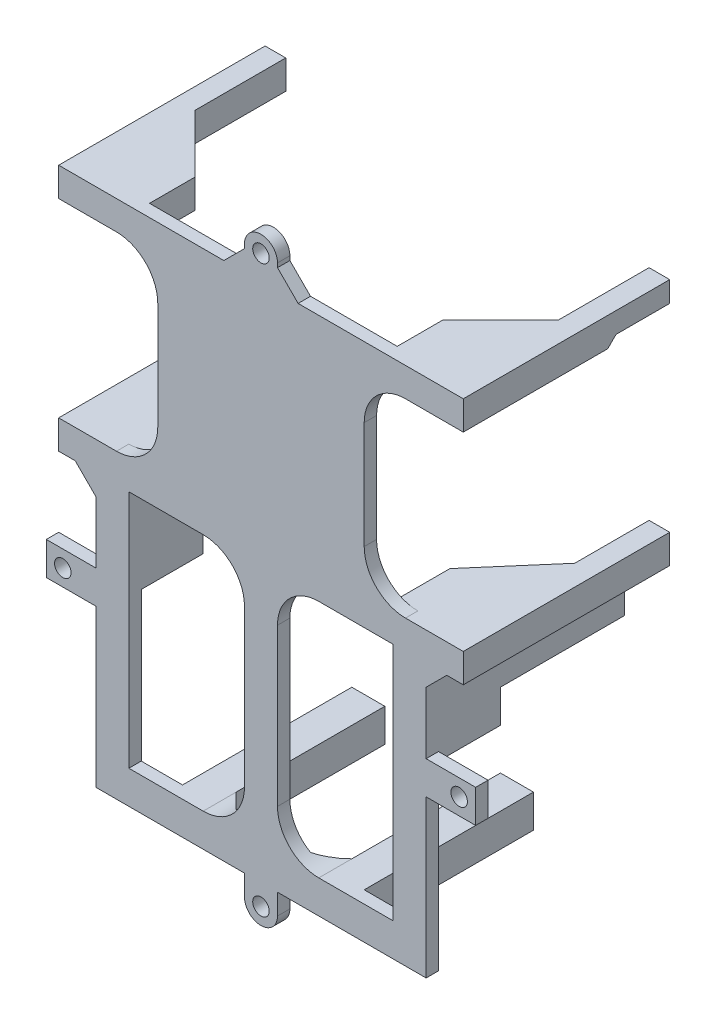
SolidWorks part; units mm, degrees
ref_plane "Piano frontale" through (0, 0, 0) normal (0, 0, 1) x (1, 0, 0)
ref_plane "Piano superiore" through (0, 0, 0) normal (0, 1, 0) x (1, 0, 0)
ref_plane "Piano destro" through (0, 0, 0) normal (1, 0, 0) x (0, 0, -1)
sketch "Schizzo1" plane through (0, 0, 0) normal (0, 0, 1) x (1, 0, 0)
  line L0 (0, 0) -> (0, 70) construction
  line L1 (-48, 23) -> (48, 23) construction
  line L2 (0, 70) -> (0, 0) construction
  line L3 (4, 70) -> (4, 27)
  line L4 (-4, 70) -> (-4, 27)
  line L5 (-48, 23) -> (48, 23) construction
  line L6 (52, 27) -> (52, 18)
  line L7 (-52, 27) -> (-52, 18)
  line L8 (4, 18) -> (4, -16)
  line L9 (4, 27) -> (52, 27)
  line L10 (-4, 18) -> (-4, -16)
  line L11 (4, 18) -> (52, 18)
  line L12 (-4, 18) -> (-52, 18)
  line L13 (-4, 27) -> (-52, 27)
  line L14 (-48, -20) -> (48, -20) construction
  line L15 (-4, -24) -> (-4, -67)
  line L16 (-52, -16) -> (-4, -16)
  line L17 (-52, -16) -> (-52, -24)
  line L18 (-52, -24) -> (-4, -24)
  line L19 (52, -16) -> (52, -24)
  line L20 (4, -16) -> (52, -16)
  line L21 (4, -24) -> (4, -67)
  line L22 (4, -24) -> (52, -24)
  circle A0 centre (0, 70) radius 2
  circle A1 centre (48, 23) radius 2
  circle A2 centre (-48, 23) radius 2
  arc A3 (4, 70) -> (-4, 70) centre (0, 70) ccw
  arc A4 (-4, -67) -> (4, -67) centre (0, -67) ccw
  circle A5 centre (0, -67) radius 2
  circle A6 centre (-48, -20) radius 2
  circle A7 centre (48, -20) radius 2
  point P8 (0, 35)
  point P13 (0, 20)
  dimension "D1" = 4
  dimension "D2" = 4
  dimension "D3" = 4
  dimension "D10" = 137
  dimension "D11" = 4
  dimension "D6" = 4
  dimension "D18" = 4
  dimension "D19" = 4
  dimension "D4" = 70
  dimension "D5" = 8
  dimension "D7" = 23
  dimension "D8" = 48
  dimension "D9" = 48
  dimension "D12" = 4
  dimension "D13" = 48
  dimension "D14" = 47
  dimension "D15" = 47
  dimension "D16" = 48
  dimension "D17" = 48
  dimension "D20" = 8
  dimension "D21" = 4
extrude "Estrusione-Estrusione1" add sketch "Schizzo1" along normal blind 3
sketch "Schizzo2" plane through (0, 0, 0) normal (0, 0, 1) x (1, 0, 0)
  line L0 (-42, 57) -> (-3.9212, 57)
  line L1 (-49, 64) -> (-3.9212, 64)
  line L2 (-49, 64) -> (-49, 26)
  line L3 (-49, 4) -> (-40, 4)
  line L4 (49, 64) -> (49, 26)
  line L5 (42, 57) -> (42, 26)
  line L6 (-42, 11) -> (-3.9212, 11)
  line L7 (-42, 57) -> (-42, 26)
  line L8 (-3.9212, 64) -> (-3.9212, 57)
  line L9 (3.9902, 64) -> (3.9902, 57)
  line L10 (3.9902, 64) -> (49, 64)
  line L11 (3.9902, 57) -> (42, 57)
  line L12 (-49, 64) -> (49, 64) construction
  line L13 (-3.9212, 11) -> (-3.9212, 4)
  line L14 (-42, 57) -> (42, 57) construction
  line L15 (3.9902, 11) -> (3.9902, 4)
  line L16 (3.9902, 11) -> (42, 11)
  line L17 (3.9902, 4) -> (32, 4)
  line L18 (-42, 11) -> (42, 11) construction
  line L19 (49, 26) -> (42, 26)
  line L20 (-49, 4) -> (49, 4) construction
  line L22 (-32, 4) -> (-3.9212, 4)
  line L23 (-49, 18) -> (-42, 18)
  line L24 (-40, 4) -> (-40, -62)
  line L25 (-40, -62) -> (40, -62)
  line L26 (-42, 26) -> (-49, 26)
  line L27 (42, 18) -> (42, 11)
  line L28 (49, 18) -> (49, 4)
  line L29 (42, 57) -> (42, 11) construction
  line L30 (-49, 18) -> (-49, 4)
  line L31 (49, 64) -> (49, 4) construction
  line L32 (-42, 18) -> (-42, 11)
  line L33 (-49, 64) -> (-49, 4) construction
  line L34 (42, 18) -> (49, 18)
  line L35 (-42, 57) -> (-42, 11) construction
  line L36 (40, 4) -> (40, -62)
  line L37 (40, 4) -> (49, 4)
  line L39 (-32, 4) -> (-32, -54)
  line L40 (-32, -54) -> (32, -54)
  line L41 (32, 4) -> (32, -54)
  circle A0 centre (0, 70) radius 2 construction
  circle A1 centre (0, -67) radius 2 construction
  dimension "D9" = 5
  dimension "D1" = 98
  dimension "D2" = 49
  dimension "D3" = 60
  dimension "D4" = 6
  dimension "D6" = 80
  dimension "D7" = 40
  dimension "D8" = 8
  dimension "D10" = 8
  dimension "D11" = 8
  dimension "D5" = 7
extrude "Estrusione-Estrusione2" add sketch "Schizzo2" along normal blind 3
sketch "Schizzo3" plane through (0, 0, 0) normal (0, 0, -1) x (-1, 0, 0)
  line L0 (-44, 59) -> (-49, 64) construction
  line L1 (-49, 64) -> (-44, 64)
  line L2 (-49, 64) -> (-49, 59)
  line L3 (-49, 59) -> (-44, 59)
  line L4 (-44, 64) -> (-44, 59)
  line L5 (49, 64) -> (44, 64)
  line L6 (49, 64) -> (49, 59)
  line L7 (49, 59) -> (44, 59)
  line L8 (44, 64) -> (44, 59)
  line L9 (49, 4) -> (44, 4)
  line L10 (49, 4) -> (49, 9)
  line L11 (49, 9) -> (44, 9)
  line L12 (44, 4) -> (44, 9)
  line L13 (-49, 4) -> (-44, 4)
  line L14 (-49, 4) -> (-49, 9)
  line L15 (-49, 9) -> (-44, 9)
  line L16 (-44, 4) -> (-44, 9)
  line L17 (44, 59) -> (49, 64) construction
  line L18 (44, 9) -> (49, 4) construction
  line L19 (-44, 9) -> (-49, 4) construction
  line L20 (-40, 4) -> (-49, 4) construction
  dimension "D1" = 5
  dimension "D2" = 5
  dimension "D3" = 5
  dimension "D4" = 5
  dimension "D5" = 5
  dimension "D6" = 5
  dimension "D7" = 5
  dimension "D8" = 5
extrude "Estrusione-Estrusione3" add sketch "Schizzo3" along normal blind 47
sketch "Schizzo4" plane through (0, 0, -47) normal (0, 0, -1) x (-1, 0, 0)
  line L0 (-49, 64) -> (-44, 59) construction
  line L1 (44, 59) -> (49, 64) construction
  line L2 (44, 9) -> (49, 4) construction
  line L3 (-49, 4) -> (-44, 9) construction
  line L4 (-49, 4) -> (-44, 4) construction
  circle A0 centre (-46.5, 61.5) radius 1.25
  circle A1 centre (46.5, 61.5) radius 1.25
  circle A2 centre (46.5, 6.5) radius 1.25
  circle A3 centre (-46.5, 6.5) radius 1.25
  dimension "D1" = 2.5
  dimension "D2" = 2.5
  dimension "D3" = 2.5
  dimension "D4" = 2.5
extrude "Taglio-Estrusione1" cut sketch "Schizzo4" against normal blind 15
sketch "Schizzo5" plane through (0, 4, 0) normal (0, -1, 0) x (1, 0, 0)
  line L0 (-44, 0) -> (-19, 0)
  line L1 (-44, 0) -> (-40, 0) construction
  line L2 (-19, 0) -> (-44, -29)
  line L3 (-44, -47) -> (-44, 0) construction
  line L4 (-44, -29) -> (-44, 0)
  line L5 (19, 0) -> (44, 0)
  line L6 (40, 0) -> (44, 0) construction
  line L7 (4, 0) -> (32, 0) construction
  line L9 (44, 0) -> (44, -29)
  line L10 (44, -47) -> (44, 0) construction
  line L11 (44, -29) -> (19, 0)
  dimension "D1" = 25
  dimension "D2" = 29
  dimension "D3" = 25
  dimension "D4" = 29
extrude "Estrusione-Estrusione4" add sketch "Schizzo5" against normal blind 5
sketch "Schizzo6" plane through (0, 64, 0) normal (0, 1, 0) x (1, 0, 0)
  line L0 (-44, 25) -> (-19, 0)
  line L1 (-19, 0) -> (-44, 0)
  line L2 (-44, 0) -> (-44, 25)
  line L3 (44, 25) -> (19, 0)
  line L4 (19, 0) -> (44, 0)
  line L5 (44, 0) -> (44, 25)
extrude "Estrusione-Estrusione5" add sketch "Schizzo6" against normal blind 5
sketch "Schizzo9" plane through (0, 0, 0) normal (0, 0, -1) x (-1, 0, 0)
  line L0 (-4, 57) -> (-42, 57) construction
  line L1 (-25, 57) -> (25, 57)
  line L2 (-25, 57) -> (-25, 11)
  line L3 (-25, 11) -> (25, 11)
  line L4 (25, 57) -> (25, 11)
  line L5 (4, 11) -> (42, 11) construction
  circle A0 centre (0, 70) radius 2 construction
  dimension "D1" = 50
  dimension "D2" = 25
extrude "Estrusione-Estrusione8" add sketch "Schizzo9" against normal blind 3
chamfer "Smusso1" distance 5 angle 45 2 edges at (-4, 64, 1.5) (4, 64, 1.5)
sketch "Schizzo11" plane through (0, 0, 0) normal (0, 0, -1) x (-1, 0, 0)
  line L1 (-42, 57) -> (-25, 57)
  line L2 (-42, 57) -> (-42, 11)
  line L3 (-42, 11) -> (-25, 11)
  line L4 (-25, 57) -> (-25, 11)
  line L5 (25, 57) -> (42, 57)
  line L6 (25, 57) -> (25, 11)
  line L7 (25, 11) -> (42, 11)
  line L8 (42, 57) -> (42, 11)
  line L9 (-32, 4) -> (32, 4)
  line L10 (-32, 4) -> (-32, -54)
  line L11 (-32, -54) -> (32, -54)
  line L12 (32, 4) -> (32, -54)
extrude "Taglio-Estrusione3" cut sketch "Schizzo11" against normal blind 10
sketch "Schizzo12" plane through (0, 4, 0) normal (0, -1, 0) x (1, 0, 0)
  line L0 (-40, 0) -> (-4, 0) construction
  line L1 (-30, 0) -> (30, 0)
  line L2 (-30, 0) -> (-30, -20)
  line L3 (-30, -20) -> (30, -20)
  line L4 (30, 0) -> (30, -20)
  dimension "D1" = 60
  dimension "D2" = 30
  dimension "D3" = 20
extrude "Taglio-Estrusione4" cut sketch "Schizzo12" against normal blind 60
sketch "Schizzo13" plane through (0, 0, 0) normal (0, 0, -1) x (-1, 0, 0)
  line L0 (25, 11) -> (42, 11) construction
  line L1 (25, 57) -> (52, 57)
  line L2 (25, 57) -> (25, 11)
  line L3 (25, 11) -> (52, 11)
  line L4 (52, 57) -> (52, 11)
  line L5 (52, 27) -> (52, 18) construction
  line L6 (-52, 18) -> (-52, 27) construction
  line L7 (-25, 57) -> (-52, 57)
  line L8 (-25, 57) -> (-25, 11)
  line L9 (-25, 11) -> (-52, 11)
  line L10 (-52, 57) -> (-52, 11)
extrude "Taglio-Estrusione5" cut sketch "Schizzo13" against normal blind 10
fillet "Raccordo1" radius 10 4 edges at (-25, 11, 1.5) (-25, 57, 1.5) (25, 11, 1.5) (25, 57, 1.5)
sketch "Schizzo14" plane through (0, 0, 0) normal (0, 0, -1) x (-1, 0, 0)
  line L1 (-32, 4) -> (-32, -54) construction
  line L2 (-40, 4) -> (-32, 4)
  line L3 (-40, 4) -> (-40, -10)
  line L4 (-40, -10) -> (-32, -10)
  line L7 (-32, 4) -> (-32, -10)
  line L8 (40, 4) -> (40, -16) construction
  line L9 (32, 4) -> (40, 4)
  line L10 (32, 4) -> (32, -10)
  line L14 (32, -10) -> (40, -10)
  line L15 (40, 4) -> (40, -10)
  dimension "D1" = 14
  dimension "D2" = 14
extrude "Estrusione-Estrusione9" add sketch "Schizzo14" along normal blind 45
sketch "Schizzo15" plane through (0, 0, -45) normal (0, 0, -1) x (-1, 0, 0)
  line L0 (-40, -6) -> (-32, -6) construction
  line L1 (-40, 4) -> (-40, -10) construction
  line L2 (-32, -10) -> (-32, 4) construction
  line L3 (32, -6) -> (40, -6) construction
  line L4 (32, 4) -> (32, -10) construction
  line L5 (40, -10) -> (40, 4) construction
  line L6 (-40, -10) -> (-32, -10) construction
  circle A0 centre (36, -6) radius 1.85
  circle A1 centre (-36, -6) radius 1.85
  dimension "D2" = 3.7
  dimension "D3" = 3.7
  dimension "D1" = 4
extrude "Taglio-Estrusione6" cut sketch "Schizzo15" against normal blind 20
sketch "Schizzo16" plane through (0, 0, 0) normal (0, 0, -1) x (-1, 0, 0)
  line L0 (-32, -10) -> (-32, -54) construction
  line L1 (-40, -10) -> (-32, -10)
  line L2 (-40, -10) -> (-40, -18)
  line L3 (-40, -18) -> (-32, -18)
  line L4 (-32, -10) -> (-32, -18)
  line L5 (40, -24) -> (40, -62) construction
  line L6 (32, -10) -> (40, -10)
  line L7 (32, -10) -> (32, -18)
  line L8 (32, -18) -> (40, -18)
  line L9 (40, -10) -> (40, -18)
  dimension "D1" = 8
  dimension "D2" = 8
extrude "Estrusione-Estrusione10" add sketch "Schizzo16" along normal blind 15
sketch "Schizzo17" plane through (0, 0, -15) normal (0, 0, -1) x (-1, 0, 0)
  line L0 (-40, -10) -> (-32, -18) construction
  line L1 (32, -10) -> (40, -18) construction
  circle A0 centre (-36, -14) radius 1.85
  circle A1 centre (36, -14) radius 1.85
  dimension "D1" = 3.7
  dimension "D2" = 3.7
extrude "Taglio-Estrusione7" cut sketch "Schizzo17" against normal blind 15
sketch "Schizzo18" plane through (0, 0, 0) normal (0, 0, -1) x (-1, 0, 0)
  line L0 (-32, -54) -> (32, -54) construction
  line L1 (-22, -54) -> (-14, -54)
  line L2 (-22, -54) -> (-22, -62)
  line L3 (-22, -62) -> (-14, -62)
  line L4 (-14, -54) -> (-14, -62)
  line L5 (-4, -62) -> (-40, -62) construction
  line L6 (40, -62) -> (4, -62) construction
  line L7 (14, -54) -> (22, -54)
  line L8 (14, -54) -> (14, -62)
  line L9 (14, -62) -> (22, -62)
  line L10 (22, -54) -> (22, -62)
  circle A0 centre (0, -67) radius 2 construction
  dimension "D1" = 8
  dimension "D2" = 8
  dimension "D3" = 14
  dimension "D4" = 14
extrude "Estrusione-Estrusione11" add sketch "Schizzo18" along normal blind 41
chamfer "Smusso3" distance 5 angle 45 2 edges at (-14, -58, 0) (14, -58, 0)
sketch "Schizzo19" plane through (0, 0, 0) normal (0, 0, -1) x (-1, 0, 0)
  line L0 (30, 4) -> (-30, 4) construction
  line L1 (-4, 4) -> (4, 4)
  line L2 (-4, 4) -> (-4, -54)
  line L3 (-4, -54) -> (4, -54)
  line L4 (4, 4) -> (4, -54)
  line L5 (-9, -54) -> (9, -54) construction
  dimension "D1" = 4
  dimension "D2" = 8
extrude "Estrusione-Estrusione12" add sketch "Schizzo19" against normal up to surface (3 mm away) up to face at (0, 10.9474, 3)
fillet "Raccordo2" radius 10 4 edges at (4, -54, 1.5) (-4, -54, 1.5) (4, 4, 1.5) (-4, 4, 1.5)
sketch "Schizzo20" plane through (0, 0, -41) normal (0, 0, -1) x (-1, 0, 0)
  line L0 (-22, -62) -> (-14, -54) construction
  line L1 (-14, -62) -> (-14, -54) construction
  line L2 (22, -54) -> (14, -62) construction
  arc A0 (-14, -54) -> (-9, -52.6603) centre (-14, -44) ccw construction
  circle A1 centre (-18, -58) radius 1.85
  circle A2 centre (18, -58) radius 1.85
  dimension "D1" = 3.7
  dimension "D2" = 3.7
extrude "Taglio-Estrusione8" cut sketch "Schizzo20" against normal blind 15
sketch "Schizzo21" plane through (0, 0, -45) normal (0, 0, -1) x (-1, 0, 0)
  line L0 (40, -10) -> (40, 4) construction
  line L1 (-40, 4) -> (40, 4)
  line L2 (-40, 4) -> (-40, -2)
  line L3 (-40, -2) -> (40, -2)
  line L4 (40, 4) -> (40, -2)
  line L5 (-40, -10) -> (-32, -10) construction
  dimension "D1" = 8
extrude "Taglio-Estrusione9" cut sketch "Schizzo21" against normal up to surface (30 mm away) up to face at (34.15, -14, -15)
chamfer "Smusso4" distance 5 angle 45 2 edges at (-40, 4, -6) (40, 4, -6)
sketch "Schizzo22" plane through (0, 59, 0) normal (0, -1, 0) x (1, 0, 0)
  line L0 (49, 0) -> (30, 0)
  line L1 (30, 0) -> (30, -11)
  line L2 (30, -11) -> (44, -25)
  line L3 (44, -25) -> (44, -47)
  line L4 (44, -47) -> (49, -47)
  line L5 (49, -47) -> (49, 0)
  line L6 (-30, 0) -> (-49, 0)
  line L7 (-49, 0) -> (-49, -47)
  line L8 (-49, -47) -> (-44, -47)
  line L9 (-44, -47) -> (-44, -25)
  line L10 (-44, -25) -> (-30, -11)
  line L11 (-30, -11) -> (-30, 0)
extrude "Estrusione-Estrusione13" add sketch "Schizzo22" along normal up to surface (2 mm away) up to face at (42, 57, 1.5)
sketch "Schizzo23" plane through (0, 0, -47) normal (0, 0, -1) x (-1, 0, 0)
  line L0 (-44, 57) -> (-44, 64) construction
  line L1 (-49, 57) -> (-44, 57)
  line L2 (-49, 57) -> (-49, 59)
  line L3 (-49, 59) -> (-44, 59)
  line L4 (-44, 57) -> (-44, 59)
  dimension "D1" = 2
extrude "Taglio-Estrusione10" cut sketch "Schizzo23" against normal blind 15
chamfer "Smusso5" distance 2 angle 45 1 edges at (46.5, 59, -32)
sketch "Schizzo24" plane through (0, 9, 0) normal (0, 1, 0) x (1, 0, 0)
  line L0 (-49, 0) -> (-30, 0)
  line L1 (-30, 0) -> (-30, 12.76)
  line L2 (-30, 12.76) -> (-44, 29)
  line L3 (-44, 29) -> (-44, 47)
  line L4 (-44, 47) -> (-49, 47)
  line L5 (-49, 47) -> (-49, 0)
  line L6 (44, 47) -> (49, 47)
  line L7 (49, 47) -> (49, 0)
  line L8 (49, 0) -> (30, 0)
  line L9 (30, 0) -> (30, 12.76)
  line L10 (30, 12.76) -> (44, 29)
  line L11 (44, 29) -> (44, 47)
extrude "Estrusione-Estrusione14" add sketch "Schizzo24" along normal up to surface (2 mm away) up to face at (42, 11, 1.5)
